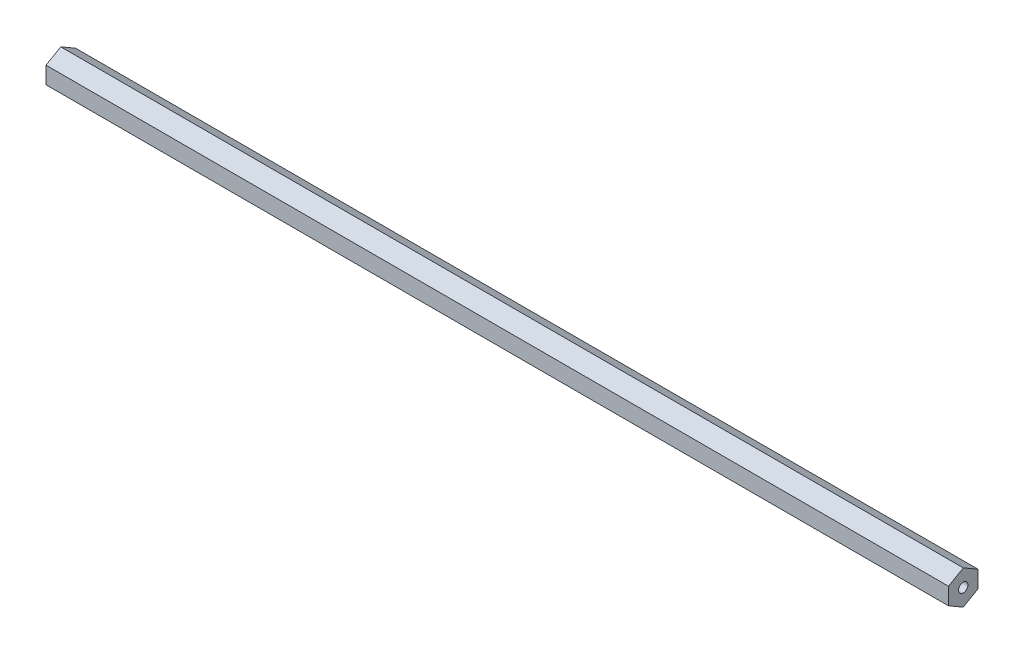
SolidWorks part; units mm, degrees
material "7075-T6 (SN)"
ref_plane "Front Plane" through (0, 0, 0) normal (0, 0, 1) x (1, 0, 0)
ref_plane "Top Plane" through (0, 0, 0) normal (0, 1, 0) x (1, 0, 0)
ref_plane "Right Plane" through (0, 0, 0) normal (1, 0, 0) x (0, 0, -1)
sketch "Sketch1" plane through (0, 0, 0) normal (1, 0, 0) x (0, 0, -1)
  line L1 (0, 7.3323) -> (-6.35, 3.6662)
  line L2 (-6.35, 3.6662) -> (-6.35, -3.6662)
  line L3 (-6.35, -3.6662) -> (0, -7.3323)
  line L4 (0, -7.3323) -> (6.35, -3.6662)
  line L5 (6.35, -3.6662) -> (6.35, 3.6662)
  line L6 (6.35, 3.6662) -> (0, 7.3323)
  circle A2 centre (0, 0) radius 6.35 construction
  dimension "D2" = 12.7
extrude "Boss-Extrude1" add sketch "Sketch1" along normal mid plane 388.874 contours L5 L6 L1 L2 L3 L4 region at (0, 0, 0)
hole_wizard "#10-32 Tapped Hole1" positions "3DSketch1" profile "Sketch2" tap size "#10-32" standard "ANSI Inch"
sketch3d "3DSketch1"
  point P0 (194.437, 0, 0)
  point P2 (-194.437, 0, 0)
sketch "Sketch2" plane through (194.437, 0, 0) normal (0, 1, 0) x (0, 0, -1)
  line L0 (0, 0) -> (0, 17.5608)
  line L1 (0, 17.5608) -> (2.0193, 16.3474)
  line L2 (2.0193, 16.3474) -> (2.0193, 0)
  line L5 (2.0193, 0) -> (0, 0)
  line L10 (0, 17.5608) -> (-2.0193, 16.3474) construction
  line L11 (0, -6.35) -> (0, 107.95) construction
  dimension "Tap Drill Dia." = 4.0386
  dimension "Tap Drill Depth" = 16.3474
  dimension "Drill Angle" = 118
cosmetic thread "Hole Thread1" parameters "D1"=13.97, "D2"=4.826
cosmetic thread "Hole Thread2" parameters "D1"=13.97, "D2"=4.826
